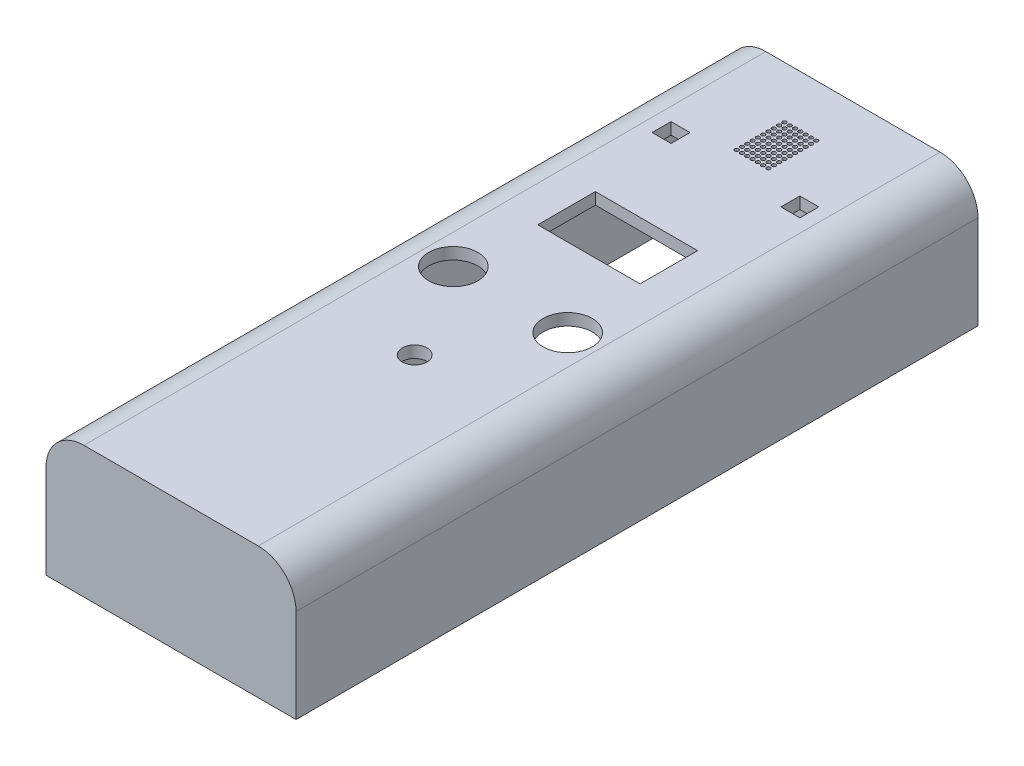
SolidWorks part; units mm, degrees
ref_plane "Front Plane" through (0, 0, 0) normal (0, 0, 1) x (1, 0, 0)
ref_plane "Top Plane" through (0, 0, 0) normal (0, 1, 0) x (1, 0, 0)
ref_plane "Right Plane" through (0, 0, 0) normal (1, 0, 0) x (0, 0, -1)
sketch "Sketch1" plane through (0, 0, 0) normal (0, 1, 0) x (1, 0, 0)
  line L1 (0, 0) -> (66, 0)
  line L2 (0, 0) -> (0, 180)
  line L3 (0, 180) -> (66, 180)
  line L4 (66, 0) -> (66, 180)
  dimension "D1" = 180
  dimension "D2" = 66
extrude "Boss-Extrude1" add sketch "Sketch1" along normal blind 34.7
sketch "Sketch2" plane through (0, 34.7, 0) normal (0, 1, 0) x (1, 0, 0)
  line L0 (33, 0) -> (33, 205.7277) construction
  line L1 (0, 0) -> (66, 0) construction
  circle A0 centre (33, 64.3) radius 3.25
  point P6 (0, 0)
  dimension "D2" = 6.5
  dimension "D1" = 64.3
sketch "Sketch3" plane through (0, 34.7, 0) normal (0, 1, 0) x (1, 0, 0)
  line L0 (33, 0) -> (33, 180) construction
  line L1 (0, 0) -> (66, 0) construction
  line L2 (66, 180) -> (0, 180) construction
  line L4 (14.4, 39.39) -> (51.6, 39.39)
  line L5 (14.4, 39.39) -> (14.4, 2.09)
  line L6 (14.4, 2.09) -> (51.6, 2.09)
  line L7 (51.6, 39.39) -> (51.6, 2.09)
  line L8 (14.4, 39.39) -> (51.6, 2.09) construction
  line L9 (14.4, 2.09) -> (51.6, 39.39) construction
  point P6 (33, 20.74)
  dimension "D1" = 37.3
  dimension "D2" = 37.2
sketch "Sketch4" plane through (0, 34.7, 0) normal (0, 1, 0) x (1, 0, 0)
  line L0 (33, 0) -> (33, 180) construction
  line L1 (0, 0) -> (66, 0) construction
  line L2 (66, 180) -> (0, 180) construction
  line L3 (0, 180) -> (0, 0) construction
  line L4 (0, 89.6) -> (66, 89.6) construction
  line L5 (66, 0) -> (66, 180) construction
  circle A0 centre (48.1, 89.6) radius 6.5
  circle A1 centre (17.9, 89.6) radius 6.5
  dimension "D2" = 13
  dimension "D3" = 13
  dimension "D1" = 89.6
  dimension "D4" = 15.1
  dimension "D5" = 15.1
sketch "Sketch5" plane through (0, 34.7, 0) normal (0, 1, 0) x (1, 0, 0)
  line L0 (33, 0) -> (33, 180) construction
  line L1 (0, 0) -> (66, 0) construction
  line L2 (66, 180) -> (0, 180) construction
  line L4 (19.5, 125.5) -> (46.5, 125.5)
  line L5 (19.5, 125.5) -> (19.5, 110.3)
  line L6 (19.5, 110.3) -> (46.5, 110.3)
  line L7 (46.5, 125.5) -> (46.5, 110.3)
  line L8 (19.5, 125.5) -> (46.5, 110.3) construction
  line L9 (19.5, 110.3) -> (46.5, 125.5) construction
  point P6 (33, 117.9)
  point P11 (0, 0)
  dimension "D1" = 15.2
  dimension "D2" = 27
  dimension "D3" = 110.3
sketch "Sketch6" plane through (0, 34.7, 0) normal (0, 1, 0) x (1, 0, 0)
  line L0 (33, 0) -> (33, 180) construction
  line L1 (0, 0) -> (66, 0) construction
  line L2 (66, 180) -> (0, 180) construction
  line L3 (0, 148.9794) -> (66, 148.9794) construction
  line L4 (27.9, 171.1486) -> (38.1, 171.1486)
  line L5 (27.9, 171.1486) -> (27.9, 158.1486)
  line L6 (27.9, 158.1486) -> (38.1, 158.1486)
  line L7 (38.1, 171.1486) -> (38.1, 158.1486)
  line L8 (27.9, 171.1486) -> (38.1, 158.1486) construction
  line L9 (27.9, 158.1486) -> (38.1, 171.1486) construction
  line L10 (0, 180) -> (0, 0) construction
  line L11 (66, 0) -> (66, 180) construction
  line L13 (47.5, 151.4794) -> (52.5, 151.4794)
  line L14 (47.5, 151.4794) -> (47.5, 146.4794)
  line L15 (47.5, 146.4794) -> (52.5, 146.4794)
  line L16 (52.5, 151.4794) -> (52.5, 146.4794)
  line L17 (47.5, 151.4794) -> (52.5, 146.4794) construction
  line L18 (47.5, 146.4794) -> (52.5, 151.4794) construction
  line L19 (18.5, 146.4794) -> (13.5, 146.4794)
  line L20 (13.5, 151.4794) -> (13.5, 146.4794)
  line L21 (18.5, 151.4794) -> (13.5, 151.4794)
  line L22 (18.5, 151.4794) -> (18.5, 146.4794)
  point P6 (33, 164.6486)
  point P17 (50, 148.9794)
  point P26 (0, 0)
  point P27 (0, 0)
  point P28 (0, 0)
  point P29 (0, 0)
  point P30 (0, 0)
  dimension "D1" = 13
  dimension "D2" = 10.2
  dimension "D3" = 5
  dimension "D4" = 5
  dimension "D5" = 17
sketch "Sketch20" plane through (0, 34.7, 0) normal (0, 1, 0) x (1, 0, 0)
  line L0 (33, 180) -> (33, 119.0875) construction
  line L1 (66, 180) -> (0, 180) construction
  line L3 (27.9, 153.2735) -> (38.1, 153.2735)
  line L4 (27.9, 153.2735) -> (27.9, 167.2735)
  line L5 (27.9, 167.2735) -> (38.1, 167.2735)
  line L6 (38.1, 153.2735) -> (38.1, 167.2735)
  line L7 (27.9, 153.2735) -> (38.1, 167.2735) construction
  line L8 (27.9, 167.2735) -> (38.1, 153.2735) construction
  point P4 (33, 160.2735)
  dimension "D1" = 14
  dimension "D2" = 10.2
fillet "Fillet1" radius 10 2 edges at (66, 34.7, -90) (0, 34.7, -90)
shell "Shell1" thickness 3.1 removed face at (33, 0, -90)
extrude "Cut-Extrude4" cut sketch "Sketch4" against normal through all contours A0 | A1
extrude "Cut-Extrude5" cut sketch "Sketch2" against normal through all contours A0
extrude "Cut-Extrude6" cut sketch "Sketch5" against normal through all contours L7 L6 L5 L4
extrude "Cut-Extrude10" cut sketch "Sketch6" against normal through all contours L15 L16 L13 L14 | L19 L20 L21 L22
sketch "Sketch31" plane through (0, 34.7, 0) normal (0, 1, 0) x (1, 0, 0)
  line L0 (27.9, 167.2735) -> (38.1, 153.2735) construction
  line L1 (27.9, 167.2735) -> (38.1, 167.2735) construction
  line L2 (27.9, 153.2735) -> (27.9, 167.2735) construction
  circle A0 centre (28.6286, 166.2735) radius 0.5
  circle A1 centre (30.0286, 166.2735) radius 0.5
  circle A2 centre (31.4286, 166.2735) radius 0.5
  circle A3 centre (32.8286, 166.2735) radius 0.5
  circle A4 centre (34.2286, 166.2735) radius 0.5
  circle A5 centre (35.6286, 166.2735) radius 0.5
  circle A6 centre (37.0286, 166.2735) radius 0.5
  circle A7 centre (30.0286, 164.8735) radius 0.5
  circle A8 centre (31.4286, 164.8735) radius 0.5
  circle A9 centre (32.8286, 164.8735) radius 0.5
  circle A10 centre (34.2286, 164.8735) radius 0.5
  circle A11 centre (35.6286, 164.8735) radius 0.5
  circle A12 centre (37.0286, 164.8735) radius 0.5
  circle A13 centre (30.0286, 163.4735) radius 0.5
  circle A14 centre (31.4286, 163.4735) radius 0.5
  circle A15 centre (32.8286, 163.4735) radius 0.5
  circle A16 centre (34.2286, 163.4735) radius 0.5
  circle A17 centre (35.6286, 163.4735) radius 0.5
  circle A18 centre (37.0286, 163.4735) radius 0.5
  circle A19 centre (30.0286, 162.0735) radius 0.5
  circle A20 centre (31.4286, 162.0735) radius 0.5
  circle A21 centre (32.8286, 162.0735) radius 0.5
  circle A22 centre (34.2286, 162.0735) radius 0.5
  circle A23 centre (35.6286, 162.0735) radius 0.5
  circle A24 centre (37.0286, 162.0735) radius 0.5
  circle A25 centre (30.0286, 160.6735) radius 0.5
  circle A26 centre (31.4286, 160.6735) radius 0.5
  circle A27 centre (32.8286, 160.6735) radius 0.5
  circle A28 centre (34.2286, 160.6735) radius 0.5
  circle A29 centre (35.6286, 160.6735) radius 0.5
  circle A30 centre (37.0286, 160.6735) radius 0.5
  circle A31 centre (30.0286, 159.2735) radius 0.5
  circle A32 centre (31.4286, 159.2735) radius 0.5
  circle A33 centre (32.8286, 159.2735) radius 0.5
  circle A34 centre (34.2286, 159.2735) radius 0.5
  circle A35 centre (35.6286, 159.2735) radius 0.5
  circle A36 centre (37.0286, 159.2735) radius 0.5
  circle A37 centre (30.0286, 157.8735) radius 0.5
  circle A38 centre (31.4286, 157.8735) radius 0.5
  circle A39 centre (32.8286, 157.8735) radius 0.5
  circle A40 centre (34.2286, 157.8735) radius 0.5
  circle A41 centre (35.6286, 157.8735) radius 0.5
  circle A42 centre (37.0286, 157.8735) radius 0.5
  circle A43 centre (30.0286, 156.4735) radius 0.5
  circle A44 centre (31.4286, 156.4735) radius 0.5
  circle A45 centre (32.8286, 156.4735) radius 0.5
  circle A46 centre (34.2286, 156.4735) radius 0.5
  circle A47 centre (35.6286, 156.4735) radius 0.5
  circle A48 centre (37.0286, 156.4735) radius 0.5
  circle A49 centre (30.0286, 155.0735) radius 0.5
  circle A50 centre (31.4286, 155.0735) radius 0.5
  circle A51 centre (32.8286, 155.0735) radius 0.5
  circle A52 centre (34.2286, 155.0735) radius 0.5
  circle A53 centre (35.6286, 155.0735) radius 0.5
  circle A54 centre (37.0286, 155.0735) radius 0.5
  circle A55 centre (30.0286, 153.6735) radius 0.5
  circle A56 centre (31.4286, 153.6735) radius 0.5
  circle A57 centre (32.8286, 153.6735) radius 0.5
  circle A58 centre (34.2286, 153.6735) radius 0.5
  circle A59 centre (35.6286, 153.6735) radius 0.5
  circle A60 centre (37.0286, 153.6735) radius 0.5
  circle A61 centre (28.6286, 164.8735) radius 0.5
  circle A62 centre (28.6286, 163.4735) radius 0.5
  circle A63 centre (28.6286, 162.0735) radius 0.5
  circle A64 centre (28.6286, 160.6735) radius 0.5
  circle A65 centre (28.6286, 159.2735) radius 0.5
  circle A66 centre (28.6286, 157.8735) radius 0.5
  circle A67 centre (28.6286, 156.4735) radius 0.5
  circle A68 centre (28.6286, 155.0735) radius 0.5
  circle A69 centre (28.6286, 153.6735) radius 0.5
  dimension "D1" = 1
  dimension "D2" = 1
  dimension "D3" = 0.7286
  dimension "D4" = 7
  dimension "D5" = 10
extrude "Cut-Extrude11" cut sketch "Sketch31" against normal through all
